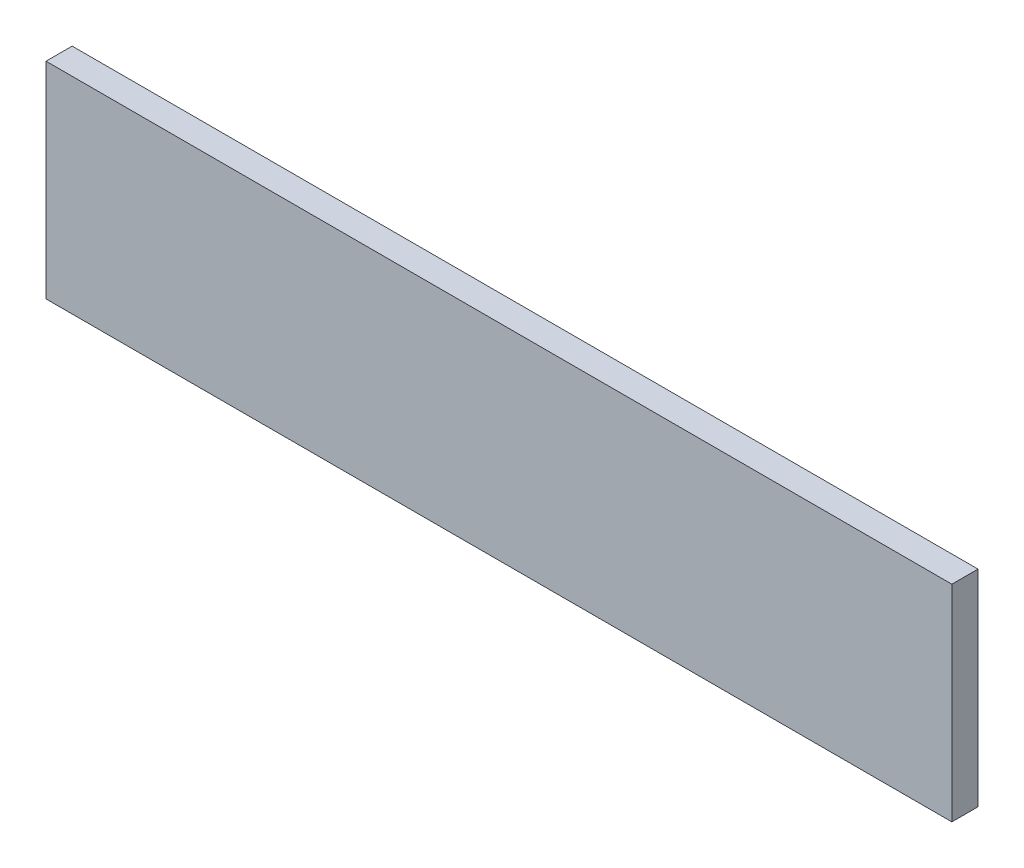
SolidWorks part; units mm, degrees
ref_plane "Front Plane" through (0, 0, 0) normal (0, 0, 1) x (1, 0, 0)
ref_plane "Top Plane" through (0, 0, 0) normal (0, 1, 0) x (1, 0, 0)
ref_plane "Right Plane" through (0, 0, 0) normal (1, 0, 0) x (0, 0, -1)
sketch "Sketch1" plane through (0, 0, 0) normal (0, 0, 1) x (1, 0, 0)
  line L1 (-110, -25) -> (110, -25)
  line L2 (-110, -25) -> (-110, 25)
  line L3 (-110, 25) -> (110, 25)
  line L4 (110, -25) -> (110, 25)
  line L5 (-110, -25) -> (110, 25) construction
  line L6 (-110, 25) -> (110, -25) construction
  point P0 (0, 0)
  dimension "D1" = 220
  dimension "D2" = 50
extrude "Boss-Extrude1" add sketch "Sketch1" along normal mid plane 6.35
